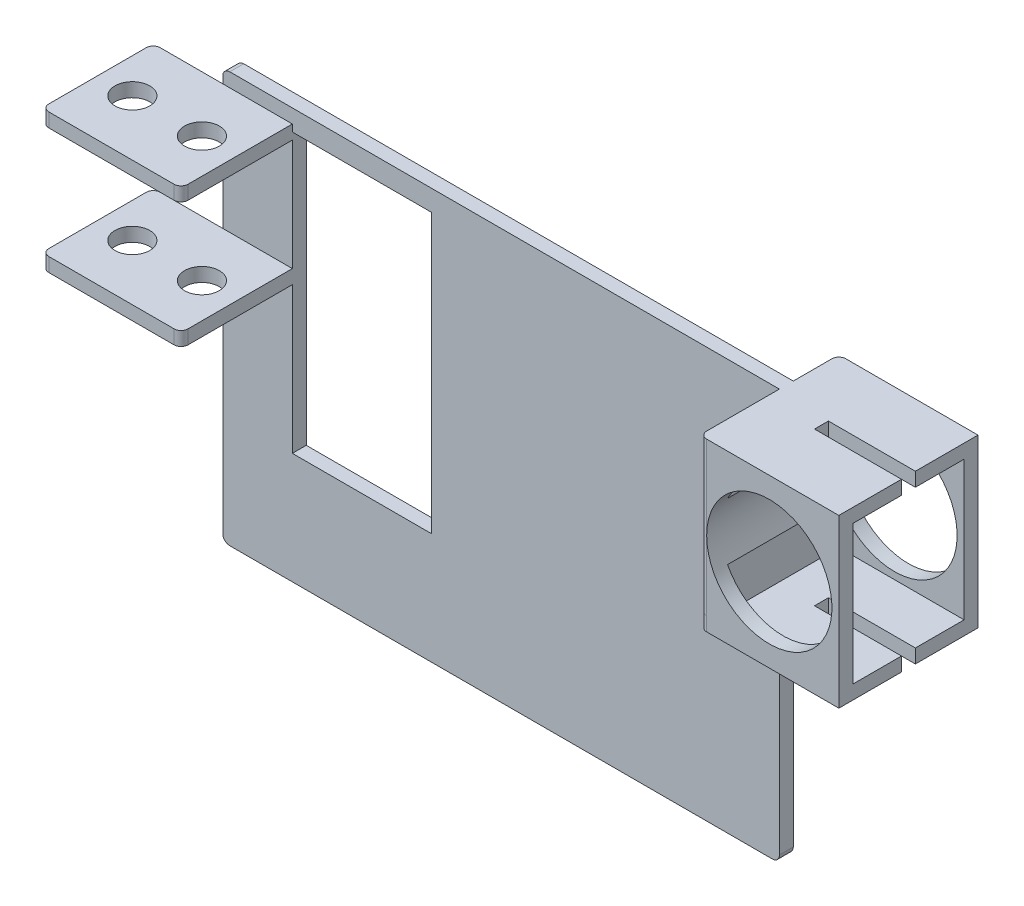
SolidWorks part; units mm, degrees
ref_plane "Front Plane" through (0, 0, 0) normal (0, 0, 1) x (1, 0, 0)
ref_plane "Top Plane" through (0, 0, 0) normal (0, 1, 0) x (1, 0, 0)
ref_plane "Right Plane" through (0, 0, 0) normal (1, 0, 0) x (0, 0, -1)
sketch "Sketch1" plane through (0, 0, 0) normal (0, 1, 0) x (1, 0, 0)
  line L0 (-2.2917, 11.0417) -> (-22.2917, 11.0417)
  line L1 (-22.2917, 11.0417) -> (-22.2917, -8.9583)
  line L2 (-22.2917, -8.9583) -> (-2.2917, -8.9583)
  line L3 (-20.2917, 9.0417) -> (-2.2917, 9.0417)
  line L4 (-20.2917, 9.0417) -> (-20.2917, -6.9583)
  line L5 (-20.2917, -6.9583) -> (-2.2917, -6.9583)
  line L6 (-2.2917, -6.9583) -> (-2.2917, -8.9583)
  line L7 (-2.2917, 9.0417) -> (-2.2917, 11.0417)
  dimension "D1" = 20
  dimension "D2" = 20
  dimension "D3" = 20
  dimension "D4" = 2
  dimension "D5" = 2
  dimension "D6" = 2
extrude "Boss-Extrude1" add sketch "Sketch1" along normal blind 20
fillet "Fillet1" radius 1 2 edges at (-22.2917, 10, -11.0417) (-22.2917, 10, 8.9583)
sketch "Sketch2" plane through (0, 0, 8.9583) normal (0, 0, 1) x (1, 0, 0)
  line L0 (-21.2917, 0) -> (-2.2917, 0) construction
  line L1 (-2.2917, 20) -> (-2.2917, 0) construction
  circle A0 centre (-12.2917, 10) radius 9
  dimension "D3" = 18
  dimension "D1" = 10
  dimension "D2" = 10
extrude "Cut-Extrude1" cut sketch "Sketch2" against normal blind 20
sketch "Sketch3" plane through (0, 20, 0) normal (0, 1, 0) x (1, 0, 0)
  line L0 (-21.2917, 11.0417) -> (-2.2917, 11.0417)
  line L1 (-2.2917, 11.0417) -> (-2.2917, -8.9583)
  line L2 (-2.2917, -8.9583) -> (-22.2917, -8.9583)
  line L3 (-22.2917, -8.9583) -> (-22.2917, 11.0417)
  line L4 (-22.2917, 11.0417) -> (-21.2917, 11.0417)
  line L9 (-2.2917, 2.3778) -> (-2.2917, 0.3778)
  line M10 (-2.2917, 11.0417) -> (-21.2917, 11.0417)
  arc M11 (-21.2917, 11.0417) -> (-22.2917, 10.0417) centre (-21.2917, 10.0417) ccw
  line M12 (-22.2917, 10.0417) -> (-22.2917, -7.9583)
  arc M13 (-22.2917, -7.9583) -> (-21.2917, -8.9583) centre (-21.2917, -7.9583) ccw
  line M14 (-21.2917, -8.9583) -> (-2.2917, -8.9583)
  line M15 (-2.2917, -8.9583) -> (-2.2917, -6.9583)
  line M16 (-2.2917, -6.9583) -> (-20.2917, -6.9583)
  line M17 (-20.2917, -6.9583) -> (-20.2917, 9.0417)
  line M18 (-20.2917, 9.0417) -> (-2.2917, 9.0417)
  line M19 (-2.2917, 9.0417) -> (-2.2917, 11.0417)
  dimension "D1" = 20
extrude "Boss-Extrude2" add sketch "Sketch3" along normal blind 2 contours L1 M18 M17 M16 | M19 M10 M11 M12 M13 M14 M15 M16 M17 M18 region at (-11.7917, 20, -10.7588) region at (-11.2917, 20, -1.0417)
sketch "Sketch4" plane through (0, 0, 0) normal (0, -1, 0) x (1, 0, 0)
  line L0 (-2.2917, 8.9583) -> (-2.2917, -11.0417)
  line L1 (-2.2917, -11.0417) -> (-22.2917, -11.0417)
  line L2 (-22.2917, -11.0417) -> (-22.2917, 8.9583)
  line L3 (-22.2917, 8.9583) -> (-2.2917, 8.9583)
  dimension "D1" = 20
  dimension "D2" = 20
extrude "Boss-Extrude3" add sketch "Sketch4" along normal blind 2
fillet "Fillet2" radius 1 2 edges at (-22.2917, -1, -11.0417) (-22.2917, -1, 8.9583)
sketch "Sketch5" plane through (0, 22, 0) normal (0, 1, 0) x (1, 0, 0)
  line L0 (-2.2917, 11.0417) -> (-2.2917, -8.9583) construction
  line L1 (-14.7917, 2.0417) -> (-2.2917, 2.0417)
  line L2 (-14.7917, 2.0417) -> (-14.7917, 0.0417)
  line L3 (-14.7917, 0.0417) -> (-2.2917, 0.0417)
  line L4 (-2.2917, 2.0417) -> (-2.2917, 0.0417)
  line L5 (-21.2917, -8.9583) -> (-2.2917, -8.9583) construction
  dimension "D1" = 12.5
  dimension "D2" = 2
  dimension "D3" = 9
extrude "Cut-Extrude2" cut sketch "Sketch5" against normal blind 24
sketch "Sketch6" plane through (-22.2917, 0, 0) normal (-1, 0, 0) x (0, 0, 1)
  line L0 (-2.4917, -37) -> (-4.4917, -37)
  line L5 (-4.4917, -37) -> (-4.4917, -2)
  line L6 (-10.0417, 22) -> (7.9583, 22) construction
  line L7 (-2.4917, 22) -> (-4.4917, 22)
  line L8 (-2.4917, 22) -> (-2.4917, -2)
  line L10 (-4.4917, 22) -> (-4.4917, -2)
  line L11 (7.9583, -2) -> (-10.0417, -2) construction
  line L12 (-11.0417, 10) -> (-11.0417, 22) construction
  line L13 (-2.4917, -2) -> (-2.4917, -37)
  point P6 (-3.4917, -37)
  dimension "D1" = 6.55
  dimension "D2" = 2
  dimension "D3" = 35
extrude "Boss-Extrude4" add sketch "Sketch6" along normal blind 80
fillet "Fillet3" radius 1 3 edges at (-22.2917, -37, -3.4917) (-102.2917, -37, -3.4917) (-102.2917, 22, -3.4917)
sketch "Sketch8" plane through (0, 0, -4.4917) normal (0, 0, -1) x (-1, 0, 0)
  line L0 (82.2917, 22) -> (82.2917, -40.0805) construction
  line L1 (72.2917, 19) -> (92.2917, 19)
  line L2 (72.2917, 19) -> (72.2917, -21)
  line L3 (72.2917, -21) -> (92.2917, -21)
  line L4 (92.2917, 19) -> (92.2917, -21)
  line L5 (101.2917, 22) -> (22.2917, 22) construction
  line L6 (12.2917, 10) -> (131.172, 10) construction
  circle A0 centre (12.2917, 10) radius 9 construction
  circle A1 centre (12.2917, 10) radius 7.1139
  dimension "D4" = 70
  dimension "D1" = 20
  dimension "D2" = 40
  dimension "D3" = 10
  dimension "D5" = 9
extrude "Cut-Extrude3" cut sketch "Sketch8" against normal blind 2
sketch "Sketch9" plane through (0, 0, -2.4917) normal (0, 0, 1) x (1, 0, 0)
  line L0 (-92.824, 20) -> (-112.2917, 20)
  line L1 (-112.2917, 20) -> (-112.2917, 18)
  line L2 (-112.2917, 18) -> (-92.2917, 18)
  line L3 (-92.2917, -21) -> (-92.2917, 19) construction
  line L4 (-92.2917, 18) -> (-92.2917, 20)
  line L5 (-92.2917, 20) -> (-92.824, 20)
  line L6 (-92.2917, 0) -> (-92.2917, 2)
  line L7 (-92.2917, 2) -> (-112.2917, 2)
  line L8 (-112.2917, 2) -> (-112.2917, 0)
  line L9 (-112.2917, 0) -> (-92.2917, 0)
  line L10 (-101.2917, 22) -> (-22.2917, 22) construction
  point P13 (-112.2917, 1)
  dimension "D1" = 2
  dimension "D2" = 2
  dimension "D3" = 2
  dimension "D4" = 16
  dimension "D5" = 20
  dimension "D6" = 20
extrude "Boss-Extrude5" add sketch "Sketch9" along normal blind 16
fillet "Fillet4" radius 1 6 edges at (-112.2917, 1, -2.4917) (-112.2917, 19, -2.4917) (-112.2917, 1, 13.5083) (-92.2917, 1, 13.5083) (-92.2917, 19, 13.5083) (-112.2917, 19, 13.5083)
sketch "Sketch10" plane through (0, 20, 0) normal (0, 1, 0) x (1, 0, 0)
  line L0 (-102.2917, 2.4917) -> (-111.2917, 2.4917) construction
  line L1 (-92.2917, 2.4917) -> (-102.2917, 2.4917) construction
  line L2 (-92.2917, -12.5083) -> (-92.2917, 2.4917) construction
  circle A0 centre (-97.2917, -5.5083) radius 2.5
  circle A1 centre (-107.2917, -5.5083) radius 2.5
  dimension "D1" = 5
  dimension "D2" = 5
  dimension "D3" = 10
  dimension "D4" = 8
  dimension "D5" = 8
  dimension "D6" = 5
extrude "Cut-Extrude4" cut sketch "Sketch10" against normal blind 20
